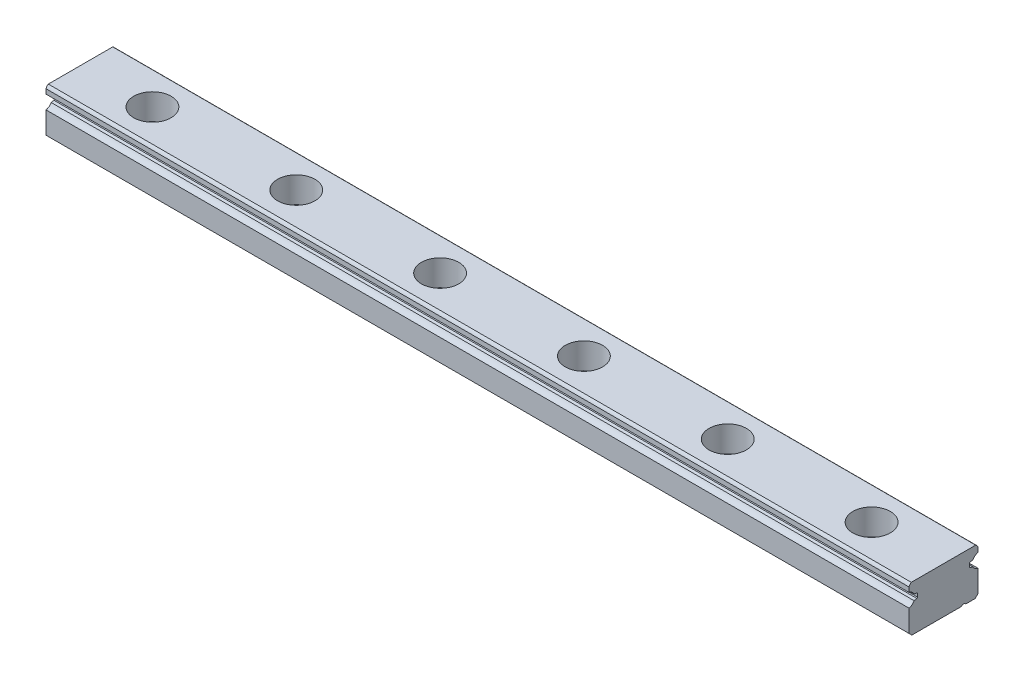
SolidWorks part; units mm, degrees
ref_plane "Front Plane" through (0, 0, 0) normal (0, 0, 1) x (1, 0, 0)
ref_plane "Top Plane" through (0, 0, 0) normal (0, 1, 0) x (1, 0, 0)
ref_plane "Right Plane" through (0, 0, 0) normal (1, 0, 0) x (0, 0, -1)
sketch "Sketch1" plane through (0, 0, 0) normal (1, 0, 0) x (0, 0, -1)
  line L0 (-6, 0.5) -> (-5.5, 0)
  line L1 (-5.5, 0) -> (5.5, 0)
  line L2 (5.5, 0) -> (6, 0.5)
  line L3 (6, 0.5) -> (6, 4.3168)
  line L4 (5.1128, 4.992) -> (4.622, 5.0785)
  line L5 (4.5, 5.217) -> (4.5, 5.783)
  line L6 (4.622, 5.9215) -> (5.1128, 6.008)
  line L7 (6, 6.6832) -> (6, 7.5)
  line L8 (5.6, 8) -> (-5.6, 8)
  line L9 (-6, 7.5) -> (-6, 6.6832)
  line L10 (-5.1128, 6.008) -> (-4.622, 5.9215)
  line L11 (-4.5, 5.783) -> (-4.5, 5.217)
  line L12 (-4.622, 5.0785) -> (-5.1128, 4.992)
  line L13 (-6, 4.3168) -> (-6, 0.5)
  arc A0 (6, 4.3168) -> (5.1128, 4.992) centre (6.2, 5.5) cw
  arc A1 (4.622, 5.0785) -> (4.5, 5.217) centre (4.853, 5.4051) cw
  arc A2 (4.5, 5.783) -> (4.622, 5.9215) centre (4.853, 5.5949) cw
  arc A3 (5.1128, 6.008) -> (6, 6.6832) centre (6.2, 5.5) cw
  arc A4 (6, 7.5) -> (5.6, 8) centre (5.0602, 7.1582) ccw
  arc A5 (-5.6, 8) -> (-6, 7.5) centre (-5.0602, 7.1582) ccw
  arc A6 (-6, 6.6832) -> (-5.1128, 6.008) centre (-6.2, 5.5) cw
  arc A7 (-4.622, 5.9215) -> (-4.5, 5.783) centre (-4.853, 5.5949) cw
  arc A8 (-4.5, 5.217) -> (-4.622, 5.0785) centre (-4.853, 5.4051) cw
  arc A9 (-5.1128, 4.992) -> (-6, 4.3168) centre (-6.2, 5.5) cw
extrude "Extrude1" add sketch "Sketch1" along normal blind 150
sketch "Sketch2" plane through (0, 0, 0) normal (0, 0, -1) x (-1, 0, 0)
  line L0 (-12.5, 8) -> (-9.25, 8)
  line L1 (-9.25, 8) -> (-9.25, 3.5)
  line L2 (-9.25, 3.5) -> (-10.75, 3.5)
  line L3 (-10.75, 3.5) -> (-10.75, 0.2)
  line L4 (-10.75, 0.2) -> (-10.55, 0)
  line L5 (-10.55, 0) -> (-12.5, 0)
  line L6 (-150, 0) -> (0, 0) construction
  line L7 (-12.5, 0) -> (-12.5, 8) construction
  line L8 (-150, 8) -> (0, 8) construction
  line L9 (0, 4.3168) -> (0, 0.5) construction
  line L10 (-12.5, 8) -> (-12.5, 0)
  dimension "D1" = 12.5
  dimension "D2" = 3.5
  dimension "D3" = 3.9
  dimension "D4" = 4.5
  dimension "D5" = 6.5
  dimension "D6" = 45
revolve "Cut-Revolve1" cut sketch "Sketch2" angle 360 about L7 reverse direction yes
sketch "Sketch3" plane through (125, 0, 0) normal (0, 0, -1) x (-1, 0, 0)
  line L0 (-12.5, 8) -> (-9.25, 8)
  line L1 (-9.25, 8) -> (-9.25, 3.5)
  line L2 (-9.25, 3.5) -> (-10.75, 3.5)
  line L3 (-10.75, 3.5) -> (-10.75, 0.2)
  line L4 (-10.75, 0.2) -> (-10.55, 0)
  line L5 (-10.55, 0) -> (-12.5, 0)
  line L6 (-25, 4.3168) -> (-25, 0.5) construction
  line L7 (-12.5, 0) -> (-12.5, 8) construction
  line L8 (-25, 0) -> (125, 0) construction
  line L9 (-25, 8) -> (125, 8) construction
  line L10 (-12.5, 8) -> (-12.5, 0)
  dimension "D1" = 3.5
  dimension "D2" = 12.5
  dimension "D3" = 3.9
  dimension "D4" = 45
  dimension "D5" = 4.5
  dimension "D6" = 6.5
revolve "Cut-Revolve2" cut sketch "Sketch3" angle 360 about L7 reverse direction yes
sketch "Sketch8" plane through (0, 0, 0) normal (1, 0, 0) x (0, 0, -1)
  circle A0 centre (3.5, -0.3) radius 0.5
extrude "Extrude2" cut sketch "Sketch8" along normal blind 150
ref_axis "Axis1" through (-7.5, 0, 0) along (1, 0, 0)
pattern_linear "LPattern1" count 5 spacing 25 along (-1, 0, 0) of "Cut-Revolve2"
